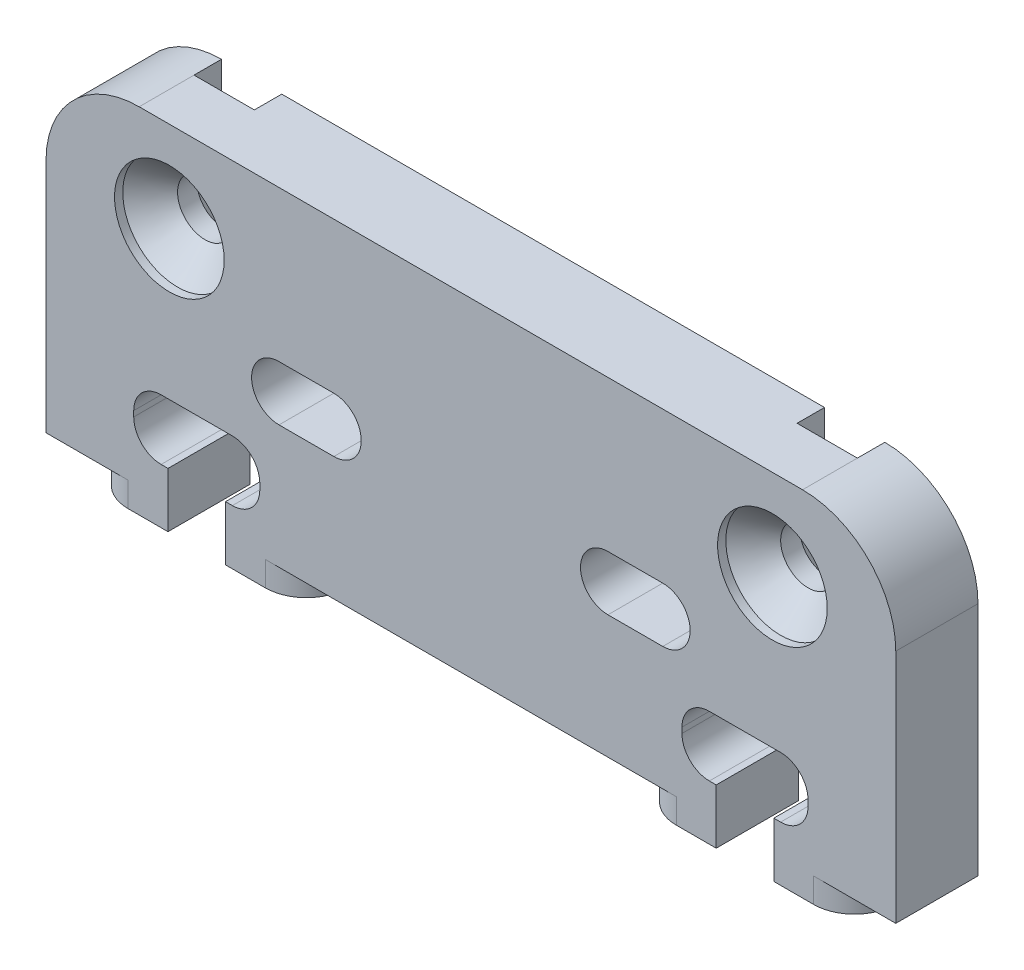
SolidWorks part; units mm, degrees
ref_plane "Front Plane" through (0, 0, 0) normal (0, 0, 1) x (1, 0, 0)
ref_plane "Top Plane" through (0, 0, 0) normal (0, 1, 0) x (1, 0, 0)
ref_plane "Right Plane" through (0, 0, 0) normal (1, 0, 0) x (0, 0, -1)
sketch "Sketch1" plane through (0, 0, 0) normal (0, 0, 1) x (1, 0, 0)
  line L0 (-10, -6.9) -> (-10, 6) construction
  line L1 (-15.5, 6) -> (15.5, 6)
  line L2 (-15.5, 6) -> (-15.5, -6)
  line L3 (-15.5, -6) -> (15.5, -6)
  line L4 (15.5, 6) -> (15.5, -6)
  line L5 (-15.5, 6) -> (15.5, -6) construction
  line L6 (-15.5, -6) -> (15.5, 6) construction
  line L7 (-15.5, -6) -> (-6, -6)
  line L9 (-14, -6.9) -> (-6, -6.9)
  line L10 (-6, -6) -> (-6, -6.9)
  line L11 (0, 6) -> (0, -6) construction
  line L12 (-11.05, -4.9) -> (-8.95, -4.9)
  line L13 (-11.05, -4.9) -> (-11.05, -6.9)
  line L14 (-11.05, -6.9) -> (-8.95, -6.9)
  line L15 (-8.95, -4.9) -> (-8.95, -6.9)
  line L16 (-11.05, -4.9) -> (-8.95, -6.9) construction
  line L17 (-11.05, -6.9) -> (-8.95, -4.9) construction
  line L18 (-12.3, -2.7) -> (-7.7, -2.7)
  line L19 (-12.3, -2.7) -> (-12.3, -4.9)
  line L20 (-12.3, -4.9) -> (-7.7, -4.9)
  line L21 (-7.7, -2.7) -> (-7.7, -4.9)
  line L22 (-12.3, -2.7) -> (-7.7, -4.9) construction
  line L23 (-12.3, -4.9) -> (-7.7, -2.7) construction
  line L24 (12.3, -2.7) -> (7.7, -2.7)
  line L25 (12.3, -2.7) -> (12.3, -4.9)
  line L26 (12.3, -4.9) -> (7.7, -4.9)
  line L27 (7.7, -2.7) -> (7.7, -4.9)
  line L28 (11.05, -4.9) -> (8.95, -4.9)
  line L29 (11.05, -4.9) -> (11.05, -6.9)
  line L30 (11.05, -6.9) -> (8.95, -6.9)
  line L31 (8.95, -4.9) -> (8.95, -6.9)
  line L32 (15.5, -6) -> (6, -6)
  line L33 (6, -6) -> (6, -6.9)
  line L34 (14, -6.9) -> (6, -6.9)
  line L36 (-14, -6.9) -> (-14, -6)
  line L37 (14, -6.9) -> (14, -6)
  line L38 (10, -2.7) -> (10, -6.9) construction
  line L39 (7, -0.5) -> (5, -0.5) construction
  line L40 (7, -1.5) -> (5, -1.5)
  line L41 (7, 0.5) -> (5, 0.5)
  line L42 (-7, -0.5) -> (-5, -0.5) construction
  line L43 (-7, -1.5) -> (-5, -1.5)
  line L44 (-7, 0.5) -> (-5, 0.5)
  arc A0 (7, -1.5) -> (7, 0.5) centre (7, -0.5) ccw
  arc A1 (5, 0.5) -> (5, -1.5) centre (5, -0.5) ccw
  arc A2 (-7, -1.5) -> (-7, 0.5) centre (-7, -0.5) cw
  arc A3 (-5, 0.5) -> (-5, -1.5) centre (-5, -0.5) cw
  point P0 (0, 0)
  point P11 (-10, -5.9)
  point P16 (-10, -3.8)
  point P40 (6, -0.5)
  point P47 (-6, -0.5)
  dimension "D1" = 31
  dimension "D2" = 12
  dimension "D3" = 0.9
  dimension "D4" = 8
  dimension "D5" = 2.1
  dimension "D6" = 2
  dimension "D7" = 2.2
  dimension "D8" = 4.6
  dimension "D9" = 20
  dimension "D10" = 2
  dimension "D11" = 2
  dimension "D12" = 12
  dimension "D13" = 5.5
extrude "Base shape" add sketch "Sketch1" along normal blind 3 contours L31 L26 L27 L24 L25 L29 L3 L4 L1 L2 L13 L20 L19 L18 L21 L15 | L3 L15 L9 L10 | L13 L3 L9 | L34 L31 L3 L33 | L3 L29 L34 region at (0, 0.3282, 0) region at (-12.525, -6.45, 0) region at (12.525, -6.45, 0) region at (-7.475, -6.45, 0) region at (7.475, -6.45, 0)
fillet "Edge radiuses" radius 3.4 2 edges at (15.5, 6, 1.5) (-15.5, 6, 1.5)
sketch "Sketch2" plane through (0, 0, 0) normal (0, 0, -1) x (-1, 0, 0)
  line L0 (0, 6) -> (0, -6) construction
  line L10 (12.1, 6) -> (-12.1, 6) construction
  line L11 (6, -6) -> (-6, -6) construction
  line L16 (-14, -6) -> (-15.5, -6) construction
  line L17 (-12.1, 6.1) -> (-9.9, 6.1)
  line L18 (-12.1, 6.1) -> (-12.1, 0.3)
  line L19 (-11.1, -0.7) -> (-10.9, -0.7)
  line L20 (-9.9, 6.1) -> (-9.9, 0.3)
  line L21 (-12.1, 6.1) -> (-9.9, -0.7) construction
  line L22 (-12.1, -0.7) -> (-9.9, 6.1) construction
  line L23 (12.1, 6.1) -> (9.9, 6.1)
  line L24 (12.1, 6.1) -> (12.1, 0.3)
  line L25 (11.1, -0.7) -> (10.9, -0.7)
  line L26 (9.9, 6.1) -> (9.9, 0.3)
  arc A8 (-10.9, -0.7) -> (-9.9, 0.3) centre (-10.9, 0.3) ccw
  arc A9 (-12.1, 0.3) -> (-11.1, -0.7) centre (-11.1, 0.3) ccw
  arc A10 (12.1, 0.3) -> (11.1, -0.7) centre (11.1, 0.3) cw
  arc A11 (10.9, -0.7) -> (9.9, 0.3) centre (10.9, 0.3) cw
  point P6 (-11, 2.7)
  dimension "D5" = 1
  dimension "D1" = 6.8
  dimension "D2" = 2.2
  dimension "D3" = 22
  dimension "D4" = 8.7
extrude "Camera mount pockets" cut sketch "Sketch2" against normal blind 1
sketch "Sketch3" plane through (0, 0, 1) normal (0, 0, -1) x (-1, 0, 0)
  line L3 (0, 6) -> (0, -6) construction
  line L5 (6, -6) -> (-6, -6) construction
  line L6 (-11.1, -0.7) -> (-10.9, -0.7) construction
  line L7 (-12.1, 6.1) -> (-9.9, 6.1)
  line L8 (-12.1, 6.1) -> (-12.1, -0.7)
  line L9 (-12.1, -0.7) -> (-9.9, -0.7)
  line L10 (-9.9, 6.1) -> (-9.9, -0.7)
  line L11 (-12.1, 6.1) -> (-9.9, -0.7) construction
  line L12 (-12.1, -0.7) -> (-9.9, 6.1) construction
  line L13 (-12.1, 6) -> (-12.1, 0.3) construction
  circle A0 centre (-11, 2.7) radius 1
  circle A1 centre (11, 2.7) radius 1
  point P2 (-11, 2.7)
  point P17 (-11, -0.7)
  point P18 (-11, -0.7)
  point P19 (-11, -0.7)
  point P22 (-11, 2.7)
  dimension "D1" = 2
  dimension "D2" = 6.8
extrude "Camera mount holes" cut sketch "Sketch3" against normal up to next contours A0 | A1 region at (11, 2.7, 1) region at (-11, 2.7, 1)
hole_wizard "CSK for M2 Flat Head Machine Screw1" positions "Sketch4" profile "Sketch5" countersink size "M2" standard "ANSI Metric" end condition through all
sketch "Sketch4" plane through (0, 0, 3) normal (0, 0, 1) x (1, 0, 0)
  point P0 (-11, 2.7)
  point P3 (11, 2.7)
sketch "Sketch5" plane through (-11, 2.7, 3) normal (1, 0, 0) x (0, -1, 0)
  line L0 (0, 0) -> (0, 3)
  line L1 (0, 3) -> (1, 3)
  line L2 (1, 3) -> (1, 1.3)
  line L3 (1, 1.3) -> (2, 0.3)
  line L4 (2, 0.3) -> (2, 0)
  line L6 (2, 0) -> (0, 0)
  line L7 (-1, 1.3) -> (-2, 0.3) construction
  line L11 (0, -6.35) -> (0, 107.95) construction
  dimension "Thru Hole Dia." = 2
  dimension "Thru Hole Depth" = 3
  dimension "C'Sink Dia." = 4
  dimension "C'Sink Angle" = 90
  dimension "Head Clearance" = 0.3
fillet "1mm milling radiuses" radius 1 8 edges at (-7.7, -2.7, 1.5) (-7.7, -4.9, 1.5) (12.3, -4.9, 1.5) (12.3, -2.7, 1.5) (7.7, -2.7, 1.5) (7.7, -4.9, 1.5) (-12.3, -4.9, 1.5) (-12.3, -2.7, 1.5)
sketch "Sketch7" plane through (0, -6.9, 0) normal (0, -1, 0) x (1, 0, 0)
  line L0 (-14, 3) -> (-6, 0) construction
  line L1 (-12.5, 1.5) -> (-7.5, 1.5) construction
  line L2 (-12.5, 3) -> (-7.5, 3)
  line L3 (-12.5, 0) -> (-7.5, 0)
  line L4 (11.05, 0) -> (14, 0) construction
  line L5 (14, 0) -> (14, 3) construction
  line L6 (14, 3) -> (11.05, 3) construction
  line L7 (11.05, 3) -> (11.05, 0) construction
  line L8 (6, 0) -> (8.95, 0) construction
  line L9 (8.95, 0) -> (8.95, 3) construction
  line L10 (8.95, 3) -> (6, 3) construction
  line L11 (6, 3) -> (6, 0) construction
  line L12 (-14, 0) -> (-11.05, 0) construction
  line L13 (-11.05, 0) -> (-11.05, 3) construction
  line L14 (-11.05, 3) -> (-14, 3) construction
  line L15 (-14, 3) -> (-14, 0) construction
  line L16 (-8.95, 0) -> (-6, 0) construction
  line L17 (-6, 0) -> (-6, 3) construction
  line L18 (-6, 3) -> (-8.95, 3) construction
  line L19 (-8.95, 3) -> (-8.95, 0) construction
  line L20 (11.05, 0) -> (14, 0)
  line L21 (14, 0) -> (14, 3)
  line L22 (14, 3) -> (11.05, 3)
  line L23 (11.05, 3) -> (11.05, 0)
  line L24 (6, 0) -> (8.95, 0)
  line L25 (8.95, 0) -> (8.95, 3)
  line L26 (8.95, 3) -> (6, 3)
  line L27 (6, 3) -> (6, 0)
  line L28 (-14, 0) -> (-11.05, 0)
  line L29 (-11.05, 0) -> (-11.05, 3)
  line L30 (-11.05, 3) -> (-14, 3)
  line L31 (-14, 3) -> (-14, 0)
  line L32 (-8.95, 0) -> (-6, 0)
  line L33 (-6, 0) -> (-6, 3)
  line L34 (-6, 3) -> (-8.95, 3)
  line L35 (-8.95, 3) -> (-8.95, 0)
  line L36 (0, 3) -> (0, 0) construction
  line L37 (-6, 3) -> (6, 3) construction
  line L38 (-6, 0) -> (6, 0) construction
  line L39 (12.5, 1.5) -> (7.5, 1.5) construction
  line L40 (12.5, 3) -> (7.5, 3)
  line L41 (12.5, 0) -> (7.5, 0)
  arc A0 (-12.5, 3) -> (-12.5, 0) centre (-12.5, 1.5) ccw
  arc A1 (-7.5, 0) -> (-7.5, 3) centre (-7.5, 1.5) ccw
  arc A2 (12.5, 3) -> (12.5, 0) centre (12.5, 1.5) cw
  arc A3 (7.5, 0) -> (7.5, 3) centre (7.5, 1.5) cw
  point P6 (-10, 1.5)
  point P29 (10, 1.5)
  line M14 (-14, 0) -> (-11.05, 0)
  line M16 (-11.05, 3) -> (-14, 3)
  line M17 (-14, 3) -> (-14, 0)
extrude "Top plate pocket radiuses" cut sketch "Sketch7" against normal up to surface (0.9 mm away) contours A0 L31 M14 | A0 M16 M17 | A1 L33 L34 | A1 L32 L33 | L27 A3 L26 | L24 A3 L27 | L22 A2 L21 | L21 A2 L20 region at (-13.6649, -6.9, 2.6649) region at (-13.6649, -6.9, 0.3351) region at (-6.3351, -6.9, 2.6649) region at (-6.3351, -6.9, 0.3351) region at (13.6649, -6.9, 0.3351) region at (13.6649, -6.9, 2.6649) region at (6.3351, -6.9, 0.3351) region at (6.3351, -6.9, 2.6649) up to face at (14.75, -6, 1.5)
